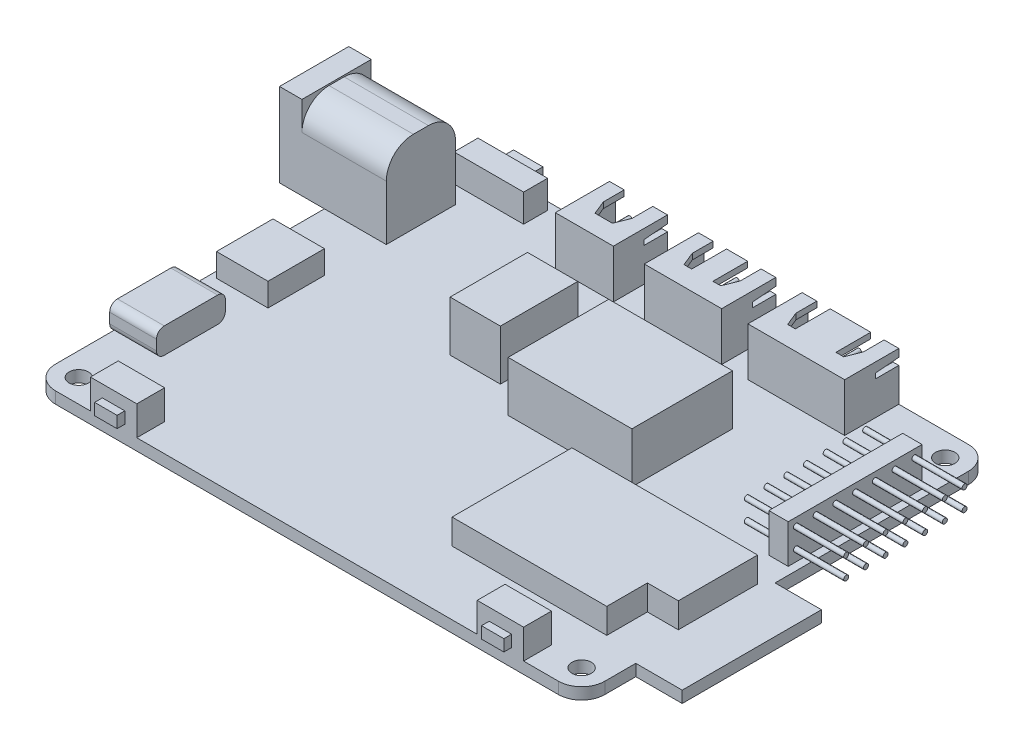
SolidWorks part; units mm, degrees
ref_plane "前视基准面" through (0, 0, 0) normal (0, 0, 1) x (1, 0, 0)
ref_plane "上视基准面" through (0, 0, 0) normal (0, 1, 0) x (1, 0, 0)
ref_plane "右视基准面" through (0, 0, 0) normal (1, 0, 0) x (0, 0, -1)
sketch "草图2" plane through (0, 0, 0) normal (0, 1, 0) x (1, 0, 0)
  line L0 (45.5671, -0.3689) -> (51.5671, -0.3689)
  line L1 (-25.4329, 27.6311) -> (45.5671, 27.6311)
  line L2 (-25.4329, 27.6311) -> (-25.4329, -25.3689)
  line L3 (-25.4329, -25.3689) -> (45.5671, -25.3689)
  line L4 (45.5671, 27.6311) -> (45.5671, -25.3689)
  line L5 (51.5671, -0.3689) -> (51.5671, -18.3689)
  line L6 (51.5671, -18.3689) -> (45.5671, -18.3689)
  dimension "D1" = 53
  dimension "D2" = 71
  dimension "D3" = 6
  dimension "D4" = 18
  dimension "D5" = 25
extrude "凸台-拉伸1" add sketch "草图2" along normal blind 1.5 contours L4 L1 L2 L3 | L6 L5 L0 L4 region at (10.0671, 0, -1.1311) region at (48.5671, 0, 9.3689)
fillet "圆角1" radius 3 4 edges at (-25.4329, 0.75, 25.3689) (-25.4329, 0.75, -27.6311) (45.5671, 0.75, -27.6311) (45.5671, 0.75, 25.3689)
sketch "草图3" plane through (0, 1.5, 0) normal (0, 1, 0) x (1, 0, 0)
  line L0 (40.5671, -1.6189) -> (44.5671, -1.6189)
  line L1 (42.0671, 19.6311) -> (44.5671, 19.6311)
  line L2 (42.0671, 19.6311) -> (42.0671, 2.3311)
  line L3 (42.0671, 2.3311) -> (44.5671, 2.3311)
  line L4 (44.5671, 19.6311) -> (44.5671, 2.3311)
  line L5 (20.5671, -1.6189) -> (40.5671, -1.6189)
  line L6 (20.5671, -1.6189) -> (20.5671, -17.1189)
  line L7 (20.5671, -17.1189) -> (40.5671, -17.1189)
  line L8 (40.5671, -1.6189) -> (40.5671, -17.1189)
  line L9 (44.5671, -1.6189) -> (44.5671, -11.8689)
  line L10 (44.5671, -11.8689) -> (40.5671, -11.8689)
  line L11 (-22.4329, -25.3689) -> (42.5671, -25.3689) construction
  line L12 (9.5671, 14.1311) -> (25.5671, 14.1311)
  line L13 (9.5671, 14.1311) -> (9.5671, 1.1311)
  line L14 (9.5671, 1.1311) -> (25.5671, 1.1311)
  line L15 (25.5671, 14.1311) -> (25.5671, 1.1311)
  line L16 (-0.9329, 14.1311) -> (5.5671, 14.1311)
  line L17 (-0.9329, 14.1311) -> (-0.9329, 4.1311)
  line L18 (-0.9329, 4.1311) -> (5.5671, 4.1311)
  line L19 (5.5671, 14.1311) -> (5.5671, 4.1311)
  line L20 (-3.8329, 27.6311) -> (3.6671, 27.6311)
  line L21 (-3.8329, 27.6311) -> (-3.8329, 20.6311)
  line L22 (-3.8329, 20.6311) -> (3.6671, 20.6311)
  line L23 (3.6671, 27.6311) -> (3.6671, 20.6311)
  line L24 (7.6671, 27.6311) -> (17.6671, 27.6311)
  line L25 (7.6671, 27.6311) -> (7.6671, 20.6311)
  line L26 (7.6671, 20.6311) -> (17.6671, 20.6311)
  line L27 (17.6671, 27.6311) -> (17.6671, 20.6311)
  line L28 (21.0671, 27.6311) -> (33.5671, 27.6311)
  line L29 (21.0671, 27.6311) -> (21.0671, 20.6311)
  line L30 (21.0671, 20.6311) -> (33.5671, 20.6311)
  line L31 (33.5671, 27.6311) -> (33.5671, 20.6311)
  line L32 (-31.2329, 21.3311) -> (-17.4329, 21.3311)
  line L33 (-31.2329, 21.3311) -> (-31.2329, 12.3811)
  line L34 (-31.2329, 12.3811) -> (-17.4329, 12.3811)
  line L35 (-17.4329, 21.3311) -> (-17.4329, 12.3811)
  line L36 (-24.6329, 4.9311) -> (-17.9729, 4.9311)
  line L37 (-24.6329, 4.9311) -> (-24.6329, -2.3689)
  line L38 (-24.6329, -2.3689) -> (-17.9729, -2.3689)
  line L39 (-17.9729, 4.9311) -> (-17.9729, -2.3689)
  line L40 (-26.7329, -6.4689) -> (-19.3829, -6.4689)
  line L41 (-26.7329, -6.4689) -> (-26.7329, -15.3689)
  line L42 (-26.7329, -15.3689) -> (-19.3829, -15.3689)
  line L43 (-19.3829, -6.4689) -> (-19.3829, -15.3689)
  line L44 (-17.9329, -21.7689) -> (-11.9329, -21.7689)
  line L45 (-17.9329, -21.7689) -> (-17.9329, -25.3689)
  line L46 (-17.9329, -25.3689) -> (-11.9329, -25.3689)
  line L47 (-11.9329, -21.7689) -> (-11.9329, -25.3689)
  line L48 (32.0671, -21.7689) -> (38.0671, -21.7689)
  line L49 (32.0671, -21.7689) -> (32.0671, -25.3689)
  line L50 (32.0671, -25.3689) -> (38.0671, -25.3689)
  line L51 (38.0671, -21.7689) -> (38.0671, -25.3689)
  line L52 (-25.4329, 24.6311) -> (-25.4329, -22.3689) construction
  line L53 (45.5671, -18.3689) -> (45.5671, -22.3689) construction
  line L54 (-22.4329, 27.6311) -> (42.5671, 27.6311) construction
  line L55 (45.5671, 24.6311) -> (45.5671, -0.3689) construction
  line L56 (51.5671, -0.3689) -> (51.5671, -18.3689) construction
  line L58 (45.5671, -0.3689) -> (51.5671, -0.3689) construction
  line L60 (-19.8329, 26.6311) -> (-10.8329, 26.6311)
  line L61 (-19.8329, 26.6311) -> (-19.8329, 23.5311)
  line L62 (-19.8329, 23.5311) -> (-10.8329, 23.5311)
  line L63 (-10.8329, 26.6311) -> (-10.8329, 23.5311)
  circle A0 centre (-22.4329, 24.6311) radius 1.25
  circle A1 centre (42.5671, 24.6311) radius 1.25
  circle A2 centre (42.5671, -22.3689) radius 1.25
  circle A3 centre (-22.4329, -22.3689) radius 1.25
  line M50 (42.5671, 27.6311) -> (-22.4329, 27.6311)
  line M52 (-25.4329, 24.6311) -> (-25.4329, -22.3689)
  line M54 (-22.4329, -25.3689) -> (42.5671, -25.3689)
  dimension "D1" = 2.5
  dimension "D2" = 6
  dimension "D3" = 3.6
  dimension "D4" = 3.6
  dimension "D5" = 6
  dimension "D6" = 13.5
  dimension "D7" = 13.5
  dimension "D8" = 13
  dimension "D9" = 16
  dimension "D10" = 13.5
  dimension "D11" = 20
  dimension "D12" = 20
  dimension "D13" = 15.5
  dimension "D14" = 10.25
  dimension "D15" = 7
  dimension "D16" = 1.25
  dimension "D17" = 4
  dimension "D18" = 17.3
  dimension "D19" = 2.5
  dimension "D20" = 1
  dimension "D21" = 8
  dimension "D22" = 7
  dimension "D23" = 0
  dimension "D24" = 7.5
  dimension "D25" = 10
  dimension "D26" = 12.5
  dimension "D27" = 4
  dimension "D28" = 3.4
  dimension "D29" = 12
  dimension "D30" = 4
  dimension "D31" = 10
  dimension "D32" = 6.5
  dimension "D33" = 9
  dimension "D34" = 3.1
  dimension "D35" = 1
  dimension "D36" = 7
  dimension "D37" = 7.3
  dimension "D38" = 6.66
  dimension "D39" = 0.8
  dimension "D40" = 8.9
  dimension "D41" = 7.35
  dimension "D42" = 1.3
  dimension "D43" = 10
  dimension "D44" = 4.1
  dimension "D45" = 7.45
  dimension "D46" = 8.95
  dimension "D47" = 13.8
  dimension "D48" = 5.8
extrude "凸台-拉伸2" add sketch "草图3" along normal blind 6.25 contours L27 L25 L26 M50 | L31 L29 L30 M50 | L23 L22 L21 L20 region at (27.3171, 1.5, -24.1311) region at (12.6671, 1.5, -24.1311)
extrude "凸台-拉伸3" add sketch "草图3<3>" along normal blind 6.5 contours L15 L12 L13 L14 | L19 L16 L17 L18 region at (17.5671, 1.5, -7.6311) region at (2.3171, 1.5, -9.1311)
sketch "草图3<3>" plane through (0, 1.5, 0) normal (0, 1, 0) x (1, 0, 0) same geometry as "草图3"
extrude "凸台-拉伸4" add sketch "草图3<4>" along normal blind 3.25 contours L8 L5 L6 L7 | L10 L9 L0 L8 region at (30.5671, 1.5, 9.3689) region at (42.5671, 1.5, 6.7439)
sketch "草图3<4>" plane through (0, 1.5, 0) normal (0, 1, 0) x (1, 0, 0) same geometry as "草图3"
extrude "切除-拉伸1" cut sketch "草图3<5>" against normal up to next contours A1 | A0 | A3 | A2
sketch "草图3<5>" plane through (0, 1.5, 0) normal (0, 1, 0) x (1, 0, 0) same geometry as "草图3"
extrude "凸台-拉伸5" add sketch "草图3<6>" along normal blind 5 contours L2 L3 L4 L1
sketch "草图3<6>" plane through (0, 1.5, 0) normal (0, 1, 0) x (1, 0, 0) same geometry as "草图3"
extrude "凸台-拉伸6" add sketch "草图3<7>" along normal blind 3.3 separate body contours L43 L40 L42 M52 region at (-22.4079, 1.5, 10.9189)
sketch "草图3<7>" plane through (0, 1.5, 0) normal (0, 1, 0) x (1, 0, 0) same geometry as "草图3"
extrude "凸台-拉伸7" add sketch "草图3<8>" along normal blind 3.8 contours L51 L48 L49 M54 | L47 L46 L45 L44 region at (35.0671, 1.5, 23.5689)
sketch "草图3<8>" plane through (0, 1.5, 0) normal (0, 1, 0) x (1, 0, 0) same geometry as "草图3"
extrude "凸台-拉伸8" add sketch "草图3<9>" along normal blind 3 contours L39 L36 L37 L38 region at (-21.3029, 1.5, -1.2811)
sketch "草图3<9>" plane through (0, 1.5, 0) normal (0, 1, 0) x (1, 0, 0) same geometry as "草图3"
extrude "凸台-拉伸9" add sketch "草图3<10>" along normal blind 10.6 contours L35 L32 L34 M52 | L33 L34 L32 M52 region at (-28.3329, 1.5, -16.8561) region at (-21.4329, 1.5, -16.8561)
sketch "草图3<10>" plane through (0, 1.5, 0) normal (0, 1, 0) x (1, 0, 0) same geometry as "草图3"
extrude "凸台-拉伸10" add sketch "草图3<11>" along normal blind 3.6 contours L63 L60 L61 L62 region at (-15.3329, 1.5, -25.0811)
sketch "草图3<11>" plane through (0, 1.5, 0) normal (0, 1, 0) x (1, 0, 0) same geometry as "草图3"
fillet "圆角2" radius 1 4 edges at (-22.4079, 4.8, 15.3689) (-22.4079, 1.5, 15.3689) (-22.4079, 4.8, 6.4689) (-22.4079, 1.5, 6.4689)
fillet "圆角3" radius 3.5 2 edges at (-24.3329, 12.1, -21.3311) (-24.3329, 12.1, -12.3811)
sketch "草图8" plane through (-31.2329, 0, 0) normal (-1, 0, 0) x (0, 0, 1)
  line L0 (-21.3311, 1.5) -> (-21.3311, 12.3)
  line L1 (-21.3311, 12.3) -> (-12.3811, 12.3)
  line L2 (-12.3811, 12.3) -> (-12.3811, 1.5)
  line L3 (-21.3311, 1.5) -> (-12.3811, 1.5) construction
  line L4 (-12.3811, 8.6) -> (-12.3811, 1.5) construction
  line L6 (-21.3311, 1.5) -> (-12.3811, 1.5)
  circle A0 centre (-16.9689, 8.6) radius 3
  circle A1 centre (-16.9689, 8.6) radius 0.75
  dimension "D2" = 6
  dimension "D3" = 1.5
  dimension "D1" = 10.8
extrude "凸台-拉伸11" add sketch "草图8" against normal blind 2.9 contours L1 L2 L6 L0
extrude "切除-拉伸2" cut sketch "草图8<7>" against normal blind 10 contours A0 A1 region at (-31.2329, 8.6, -19.8841)
sketch "草图8<7>" plane through (-31.2329, 0, 0) normal (-1, 0, 0) x (0, 0, 1) same geometry as "草图8"
fillet "圆角6" radius 0.75 1 edges at (-31.2329, 8.6, -16.2189)
sketch "草图9" plane through (0, 0, 25.3689) normal (0, 0, 1) x (1, 0, 0)
  line L1 (-16.3829, 3.7378) -> (-13.4829, 3.7378)
  line L2 (-16.3829, 3.7378) -> (-16.3829, 2.2378)
  line L3 (-16.3829, 2.2378) -> (-13.4829, 2.2378)
  line L4 (-13.4829, 3.7378) -> (-13.4829, 2.2378)
  line L5 (33.6171, 3.7378) -> (36.5171, 3.7378)
  line L6 (33.6171, 3.7378) -> (33.6171, 2.2378)
  line L7 (33.6171, 2.2378) -> (36.5171, 2.2378)
  line L8 (36.5171, 3.7378) -> (36.5171, 2.2378)
  line L9 (-11.9329, 5.3) -> (-11.9329, 1.5) construction
  line L11 (38.0671, 5.3) -> (38.0671, 1.5) construction
  dimension "D1" = 2.9
  dimension "D2" = 1.5
  dimension "D3" = 1.5
  dimension "D4" = 2.9
  dimension "D5" = 1.55
  dimension "D6" = 1.55
extrude "凸台-拉伸12" add sketch "草图9" along normal blind 1
sketch "草图10" plane through (-25.4329, 0, 0) normal (-1, 0, 0) x (0, 0, 1)
  line L0 (7.4689, 4.8) -> (14.3689, 4.8) construction
  line L1 (7.3689, 4.5) -> (14.4689, 4.5)
  line L2 (6.7689, 3.9) -> (6.7689, 2.4)
  line L3 (7.3689, 1.8) -> (14.4689, 1.8)
  line L4 (15.0689, 3.9) -> (15.0689, 2.4)
  line L5 (6.7689, 4.5) -> (15.0689, 1.8) construction
  line L6 (6.7689, 1.8) -> (15.0689, 4.5) construction
  line L7 (15.3689, 3.8) -> (15.3689, 2.5) construction
  line L9 (7.9689, 3.45) -> (13.8689, 3.45)
  line L10 (7.7689, 3.25) -> (7.7689, 3.05)
  line L11 (7.9689, 2.85) -> (13.8689, 2.85)
  line L12 (14.0689, 3.25) -> (14.0689, 3.05)
  line L13 (7.7689, 3.45) -> (14.0689, 2.85) construction
  line L14 (7.7689, 2.85) -> (14.0689, 3.45) construction
  arc A0 (6.7689, 2.4) -> (7.3689, 1.8) centre (7.3689, 2.4) ccw
  arc A1 (14.4689, 1.8) -> (15.0689, 2.4) centre (14.4689, 2.4) ccw
  arc A2 (14.4689, 4.5) -> (15.0689, 3.9) centre (14.4689, 3.9) cw
  arc A3 (7.3689, 4.5) -> (6.7689, 3.9) centre (7.3689, 3.9) ccw
  arc A4 (13.8689, 2.85) -> (14.0689, 3.05) centre (13.8689, 3.05) ccw
  arc A5 (13.8689, 3.45) -> (14.0689, 3.25) centre (13.8689, 3.25) cw
  arc A6 (7.7689, 3.05) -> (7.9689, 2.85) centre (7.9689, 3.05) ccw
  arc A7 (7.9689, 3.45) -> (7.7689, 3.25) centre (7.9689, 3.25) ccw
  point P0 (10.9189, 3.15)
  point P5 (10.9189, 3.15)
  point P8 (10.9189, 4.8)
  point P11 (15.3689, 3.15)
  dimension "D3" = 0.6
  dimension "D6" = 0.2
  dimension "D1" = 8.3
  dimension "D2" = 2.7
  dimension "D4" = 6.3
  dimension "D5" = 0.6
extrude "切除-拉伸3" cut sketch "草图10" against normal blind 5
fillet "圆角7" radius 0.2 8 edges at (-25.4329, 3.3914, 14.0103) (-25.4329, 3.15, 14.0689) (-25.4329, 2.9086, 14.0103) (-25.4329, 2.85, 10.9189) (-25.4329, 2.9086, 7.8275) (-25.4329, 3.15, 7.7689) (-25.4329, 3.3914, 7.8275) (-25.4329, 3.45, 10.9189)
sketch "草图12" plane through (0, 0, -27.6311) normal (0, 0, -1) x (-1, 0, 0)
  line L0 (-33.5671, 7.75) -> (-21.0671, 7.75) construction
  line L1 (-32.8171, 7) -> (-21.8171, 7)
  line L2 (-32.8171, 7) -> (-32.8171, 2.25)
  line L3 (-32.8171, 2.25) -> (-21.8171, 2.25)
  line L4 (-21.8171, 7) -> (-21.8171, 2.25)
  line L5 (-32.8171, 7) -> (-21.8171, 2.25) construction
  line L6 (-32.8171, 2.25) -> (-21.8171, 7) construction
  line L7 (-16.9171, 7) -> (-8.4171, 7)
  line L8 (-16.9171, 7) -> (-16.9171, 2.25)
  line L9 (-16.9171, 2.25) -> (-8.4171, 2.25)
  line L10 (-8.4171, 7) -> (-8.4171, 2.25)
  line L11 (-16.9171, 7) -> (-8.4171, 2.25) construction
  line L12 (-16.9171, 2.25) -> (-8.4171, 7) construction
  line L13 (-2.9171, 7) -> (3.0829, 7)
  line L14 (-2.9171, 7) -> (-2.9171, 2.25)
  line L15 (-2.9171, 2.25) -> (3.0829, 2.25)
  line L16 (3.0829, 7) -> (3.0829, 2.25)
  line L17 (-2.9171, 7) -> (3.0829, 2.25) construction
  line L18 (-2.9171, 2.25) -> (3.0829, 7) construction
  line L19 (-21.0671, 7.75) -> (-21.0671, 1.5) construction
  line L20 (-17.6671, 7.75) -> (-7.6671, 7.75) construction
  line L21 (-7.6671, 7.75) -> (-7.6671, 1.5) construction
  line L22 (3.8329, 7.75) -> (-3.6671, 7.75) construction
  line L23 (3.8329, 7.75) -> (3.8329, 1.5) construction
  line L24 (-33.5671, 7.75) -> (-33.5671, 1.5) construction
  line L25 (-3.6671, 7.75) -> (-3.6671, 1.5) construction
  line L26 (-17.6671, 7.75) -> (-17.6671, 1.5) construction
  line L27 (-32.8171, 6.75) -> (-33.5671, 6.75)
  line L28 (-32.8171, 6.75) -> (-32.8171, 5.95)
  line L29 (-32.8171, 5.95) -> (-33.5671, 5.95)
  line L30 (-33.5671, 6.75) -> (-33.5671, 5.95)
  line L31 (-21.8171, 6.75) -> (-21.0671, 6.75)
  line L32 (-21.8171, 6.75) -> (-21.8171, 5.95)
  line L33 (-21.8171, 5.95) -> (-21.0671, 5.95)
  line L34 (-21.0671, 6.75) -> (-21.0671, 5.95)
  line L51 (-8.4171, 6.75) -> (-7.6671, 6.75)
  line L52 (-8.4171, 6.75) -> (-8.4171, 5.95)
  line L53 (-8.4171, 5.95) -> (-7.6671, 5.95)
  line L54 (-7.6671, 6.75) -> (-7.6671, 5.95)
  line L55 (-17.6671, 6.75) -> (-16.9171, 6.75)
  line L56 (-17.6671, 6.75) -> (-17.6671, 5.95)
  line L57 (-17.6671, 5.95) -> (-16.9171, 5.95)
  line L58 (-16.9171, 6.75) -> (-16.9171, 5.95)
  line L60 (-3.6671, 6.75) -> (-2.9171, 6.75)
  line L61 (-3.6671, 6.75) -> (-3.6671, 5.95)
  line L62 (-3.6671, 5.95) -> (-2.9171, 5.95)
  line L63 (-2.9171, 6.75) -> (-2.9171, 5.95)
  line L72 (3.0829, 6.75) -> (3.8329, 6.75)
  line L73 (3.0829, 6.75) -> (3.0829, 5.95)
  line L74 (3.0829, 5.95) -> (3.8329, 5.95)
  line L75 (3.8329, 6.75) -> (3.8329, 5.95)
  circle A0 centre (-30.6921, 4.9) radius 0.3
  circle A1 centre (-28.4421, 4.9089) radius 0.3
  circle A2 centre (-26.1921, 4.9089) radius 0.3
  circle A3 centre (-23.9421, 4.9089) radius 0.3
  circle A4 centre (-14.9171, 4.9089) radius 0.3
  circle A5 centre (-12.6671, 4.9089) radius 0.3
  circle A6 centre (-10.4171, 4.9089) radius 0.3
  circle A7 centre (-1.0421, 4.9089) radius 0.3
  circle A8 centre (1.2079, 4.9089) radius 0.3
  point P0 (-27.3171, 4.625)
  point P5 (-12.6671, 4.625)
  point P10 (0.0829, 4.625)
  point P17 (-27.3171, 7.75)
  point P20 (-21.0671, 4.625)
  point P23 (-12.6671, 7.75)
  point P26 (-7.6671, 4.625)
  point P29 (0.0829, 7.75)
  point P32 (3.8329, 4.625)
  dimension "D7" = 0.6
  dimension "D19" = 2.1
  dimension "D1" = 0.75
  dimension "D2" = 0.75
  dimension "D3" = 0.75
  dimension "D4" = 0.75
  dimension "D5" = 0.75
  dimension "D6" = 0.75
  dimension "D8" = 2.25
  dimension "D9" = 2.25
  dimension "D10" = 2.25
  dimension "D11" = 2.25
  dimension "D12" = 2.25
  dimension "D13" = 2.25
  dimension "D14" = 1.125
  dimension "D15" = 0
  dimension "D16" = 1.125
  dimension "D17" = 0.8
  dimension "D18" = 1
extrude "切除-拉伸4" cut sketch "草图12" against normal blind 5.5 contours L10 L7 L8 L9 A6 A5 A4 | L16 L13 L14 L15 A8 A7 | L4 L1 L2 L3 A3 A2 A1 A0 region at (27.3171, 4.6188, -27.6311) region at (12.6671, 6.9026, -27.6311) region at (-0.0829, 4.6193, -27.6311)
sketch "草图13" plane through (33.5671, 0, 0) normal (1, 0, 0) x (0, 0, -1)
  line L0 (27.6311, 6.75) -> (24.5984, 6.5)
  line L1 (27.6311, 7.75) -> (27.6311, 1.5) construction
  line L2 (24.5984, 6.5) -> (24.5984, 5.85)
  line L3 (27.6311, 7.75) -> (20.6311, 7.75) construction
  line L4 (24.5984, 5.85) -> (27.6311, 5.85)
  line L5 (27.6311, 6.75) -> (27.6311, 5.85)
  dimension "D1" = 0.65
  dimension "D2" = 1
  dimension "D3" = 0.9
extrude "切除-拉伸5" cut sketch "草图13" against normal blind 40
sketch "草图14" plane through (0, 7.75, 0) normal (0, 1, 0) x (1, 0, 0)
  line L0 (29.9371, 27.6311) -> (29.9371, 23.1311)
  line L1 (33.5671, 27.6311) -> (21.0671, 27.6311) construction
  line L2 (29.9371, 23.1311) -> (30.9371, 23.1311)
  line L3 (30.9371, 23.1311) -> (31.6671, 24.9311)
  line L4 (31.6671, 24.9311) -> (31.6671, 27.6311)
  line L5 (29.9371, 27.6311) -> (31.6671, 27.6311)
  line L6 (27.3171, 20.6311) -> (27.3171, 16.1405) construction
  line L7 (21.0671, 20.6311) -> (33.5671, 20.6311) construction
  line L8 (33.5671, 27.6311) -> (33.5671, 20.6311) construction
  line L9 (24.6971, 27.6311) -> (22.9671, 27.6311)
  line L10 (22.9671, 24.9311) -> (22.9671, 27.6311)
  line L11 (23.6971, 23.1311) -> (22.9671, 24.9311)
  line L12 (24.6971, 23.1311) -> (23.6971, 23.1311)
  line L13 (24.6971, 27.6311) -> (24.6971, 23.1311)
  line L14 (14.0371, 27.6311) -> (14.0371, 23.1311)
  line L15 (17.6671, 27.6311) -> (7.6671, 27.6311) construction
  line L16 (14.0371, 23.1311) -> (15.0371, 23.1311)
  line L17 (15.0371, 23.1311) -> (15.7671, 24.9311)
  line L18 (15.7671, 24.9311) -> (15.7671, 27.6311)
  line L19 (0.0371, 27.6311) -> (0.0371, 23.1311)
  line L20 (-3.8329, 27.6311) -> (3.6671, 27.6311) construction
  line L21 (0.0371, 23.1311) -> (1.0371, 23.1311)
  line L22 (1.0371, 23.1311) -> (1.7671, 24.9311)
  line L23 (1.7671, 24.9311) -> (1.7671, 27.6311)
  line L24 (0.0371, 27.6311) -> (1.7671, 27.6311)
  line L25 (14.0371, 27.6311) -> (15.7671, 27.6311)
  line L26 (3.6671, 27.6311) -> (3.6671, 20.6311) construction
  line L27 (17.6671, 27.6311) -> (17.6671, 20.6311) construction
  line L28 (-0.0829, 20.6311) -> (-0.0829, 16.9175) construction
  line L29 (-3.8329, 20.6311) -> (3.6671, 20.6311) construction
  line L30 (12.6671, 20.6311) -> (12.6671, 17.7542) construction
  line L31 (7.6671, 20.6311) -> (17.6671, 20.6311) construction
  line L32 (-0.2029, 27.6311) -> (-1.9329, 27.6311)
  line L33 (-1.9329, 24.9311) -> (-1.9329, 27.6311)
  line L34 (-1.2029, 23.1311) -> (-1.9329, 24.9311)
  line L35 (-0.2029, 23.1311) -> (-1.2029, 23.1311)
  line L36 (-0.2029, 27.6311) -> (-0.2029, 23.1311)
  line L37 (-0.2029, 23.1311) -> (0.0371, 23.1311)
  line L38 (-0.2029, 27.6311) -> (0.0371, 27.6311)
  line L39 (11.2971, 27.6311) -> (9.5671, 27.6311)
  line L40 (9.5671, 24.9311) -> (9.5671, 27.6311)
  line L41 (10.2971, 23.1311) -> (9.5671, 24.9311)
  line L42 (11.2971, 23.1311) -> (10.2971, 23.1311)
  line L43 (11.2971, 27.6311) -> (11.2971, 23.1311)
  line M18 (33.5671, 27.6311) -> (21.0671, 27.6311)
  dimension "D1" = 1
  dimension "D2" = 4.5
  dimension "D3" = 1.73
  dimension "D4" = 2.7
  dimension "D5" = 1.9
  dimension "D6" = 1.9
  dimension "D7" = 1.9
extrude "切除-拉伸6" cut sketch "草图14" against normal up to next (0.75 mm away) contours L24 L19 L21 L22 L23 | L36 L32 L33 L34 L35 | L38 L36 L37 L19 | L43 L39 L40 L41 L42 | L25 L14 L16 L17 L18 | L13 L10 L11 L12 M18 | L3 L4 L0 L2 M18 region at (30.7448, 7.75, -25.5332) region at (23.8894, 7.75, -25.5332) region at (14.8448, 7.75, -25.5332) region at (0.8448, 7.75, -25.5332) region at (-0.0829, 7.75, -25.3811) region at (-1.0106, 7.75, -25.5332) region at (10.4894, 7.75, -25.5332)
sketch "草图16" plane through (44.5671, 0, 0) normal (1, 0, 0) x (0, 0, -1)
  line L0 (2.3311, 6.5) -> (2.3311, 1.5) construction
  line L2 (19.6311, 6.5) -> (2.3311, 6.5) construction
  circle A0 centre (3.3311, 5.5) radius 0.325
  dimension "D1" = 0.65
  dimension "D4" = 1
  dimension "D5" = 1
extrude "凸台-拉伸13" add sketch "草图16" along normal blind 12.85 from offset 6.35 separate body offset against normal yes
pattern_linear "阵列(线性)1" count 7 spacing 2.55 along (0, 0, -1) count 2 spacing 2.55 along (0, -1, 0) of "凸台-拉伸13"
sketch "草图18" plane through (0, 0, 0) normal (0, -1, 0) x (1, 0, 0)
  line L0 (-22.4329, 25.3689) -> (42.5671, 25.3689) construction
  line L1 (-5.4329, 17.9439) -> (14.5671, 17.9439)
  line L2 (-5.4329, 17.9439) -> (-5.4329, 13.5939)
  line L3 (-5.4329, 13.5939) -> (14.5671, 13.5939)
  line L4 (14.5671, 17.9439) -> (14.5671, 13.5939)
  line L5 (-25.4329, -24.6311) -> (-25.4329, 22.3689) construction
  circle A0 centre (4.5671, 15.7689) radius 6.325
  point P10 (14.5671, 15.7689)
  point P11 (4.5671, 17.9439)
  dimension "D1" = 12.65
  dimension "D4" = 30
  dimension "D2" = 4.35
  dimension "D3" = 9.6
  dimension "D5" = 20
extrude "凸台-拉伸14" add sketch "草图18" along normal blind 0.2 contours A0 L3 L4 L1 | A0 L1 L2 L3 | L3 A0 L1 region at (-3.5302, 0, 15.7689) region at (4.5671, 0, 15.7689) region at (12.6644, 0, 15.7689)
extrude "凸台-拉伸15" add sketch "草图18<3>" along normal blind 2.8 contours L1 A0 | L3 A0 | L3 A0 L1 region at (4.5671, 0, 19.6617) region at (4.5671, 0, 15.7689) region at (4.5671, 0, 11.8761)
sketch "草图18<3>" plane through (0, 0, 0) normal (0, -1, 0) x (1, 0, 0) same geometry as "草图18"
sketch "草图19" plane through (0, 0, -26.6311) normal (0, 0, -1) x (-1, 0, 0)
  line L1 (19.8329, 5.1) -> (10.8329, 5.1) construction
  line L2 (13.4329, 4.075) -> (17.2329, 4.075)
  line L3 (13.4329, 4.075) -> (13.4329, 2.525)
  line L4 (13.4329, 2.525) -> (17.2329, 2.525)
  line L6 (17.2329, 4.075) -> (17.2329, 2.525)
  line L7 (13.4329, 4.075) -> (17.2329, 2.525) construction
  line L8 (13.4329, 2.525) -> (17.2329, 4.075) construction
  line L9 (10.8329, 5.1) -> (10.8329, 1.5) construction
  point P0 (15.3329, 3.3)
  point P7 (15.3329, 5.1)
  point P10 (10.8329, 3.3)
  dimension "D1" = 3.8
  dimension "D2" = 1.55
extrude "凸台-拉伸16" add sketch "草图19" along normal blind 2
